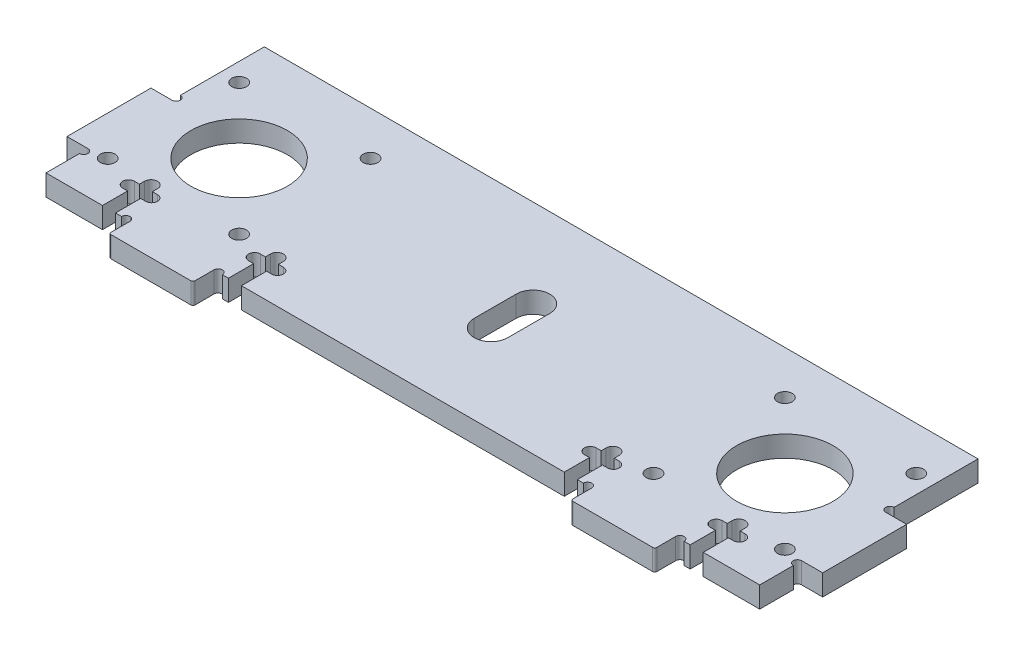
SolidWorks part; units mm, degrees
ref_plane "정면" through (0, 0, 0) normal (0, 0, 1) x (1, 0, 0)
ref_plane "윗면" through (0, 0, 0) normal (0, 1, 0) x (1, 0, 0)
ref_plane "우측면" through (0, 0, 0) normal (1, 0, 0) x (0, 0, -1)
sketch "스케치1" plane through (0, 0, 0) normal (0, 1, 0) x (1, 0, 0)
  line L1 (0, 0) -> (170, 0)
  line L2 (0, 0) -> (0, 52)
  line L3 (0, 52) -> (170, 52)
  line L4 (170, 0) -> (170, 52)
  dimension "D1" = 170
  dimension "D2" = 52
extrude "보스-돌출1" add sketch "스케치1" along normal blind 5
sketch "스케치2" plane through (0, 5, 0) normal (0, 1, 0) x (1, 0, 0)
  line L0 (85, 52) -> (85, 0) construction
  line L1 (170, 52) -> (0, 52) construction
  line L2 (0, 0) -> (170, 0) construction
  line L3 (150, 26) -> (20, 26) construction
  line L4 (134.35, 10.35) -> (165.65, 10.35) construction
  line L5 (134.35, 10.35) -> (134.35, 41.65) construction
  line L6 (134.35, 41.65) -> (165.65, 41.65) construction
  line L7 (165.65, 10.35) -> (165.65, 41.65) construction
  line L8 (134.35, 10.35) -> (165.65, 41.65) construction
  line L9 (134.35, 41.65) -> (165.65, 10.35) construction
  line L10 (170, 0) -> (170, 52) construction
  line L11 (35.65, 41.65) -> (4.35, 10.35) construction
  line L12 (35.65, 10.35) -> (4.35, 41.65) construction
  line L13 (4.35, 10.35) -> (4.35, 41.65) construction
  line L14 (35.65, 41.65) -> (4.35, 41.65) construction
  line L15 (35.65, 10.35) -> (35.65, 41.65) construction
  line L16 (35.65, 10.35) -> (4.35, 10.35) construction
  circle A0 centre (150, 26) radius 11.5
  circle A1 centre (165.65, 41.65) radius 1.75
  circle A2 centre (134.35, 41.65) radius 1.75
  circle A3 centre (165.65, 10.35) radius 1.75
  circle A4 centre (134.35, 10.35) radius 1.75
  circle A5 centre (35.65, 10.35) radius 1.75
  circle A6 centre (4.35, 10.35) radius 1.75
  circle A7 centre (35.65, 41.65) radius 1.75
  circle A8 centre (4.35, 41.65) radius 1.75
  circle A9 centre (20, 26) radius 11.5
  point P16 (170, 26)
  point P25 (85, 26)
  dimension "D1" = 23
  dimension "D3" = 3.5
  dimension "D2" = 31.3
  dimension "D4" = 20
extrude "컷-돌출1" cut sketch "스케치2" against normal blind 5
sketch "스케치3" plane through (0, 5, 0) normal (0, 1, 0) x (1, 0, 0)
  line L1 (0, 0) -> (170, 0) construction
  line L2 (130, 0) -> (150, 0)
  line L3 (130, 0) -> (130, -5)
  line L4 (130, -5) -> (150, -5)
  line L5 (150, 0) -> (150, -5)
  line L6 (130, -5) -> (40, -5) construction
  line L7 (20, 0) -> (40, 0)
  line L8 (20, 0) -> (20, -5)
  line L9 (20, -5) -> (40, -5)
  line L10 (40, 0) -> (40, -5)
  line L11 (150, -5) -> (170, -5) construction
  line L12 (170, -5) -> (170, 0) construction
  line L13 (0, 0) -> (0, -5) construction
  line L14 (0, -5) -> (20, -5) construction
  dimension "D1" = 20
  dimension "D2" = 20
  dimension "D3" = 5
extrude "보스-돌출2" add sketch "스케치3" against normal blind 5
sketch "스케치4" plane through (0, 5, 0) normal (0, 1, 0) x (1, 0, 0)
  line L0 (40, 0) -> (130, 0) construction
  line L1 (150, 0) -> (170, 0) construction
  line L2 (0, 0) -> (20, 0) construction
  circle A0 centre (129, 0) radius 1
  circle A1 centre (151, 0) radius 1
  circle A2 centre (19, 0) radius 1
  circle A3 centre (41, 0) radius 1
  dimension "D1" = 2
extrude "컷-돌출2" cut sketch "스케치4" against normal blind 5
sketch "스케치5" plane through (0, 5, 0) normal (0, 1, 0) x (1, 0, 0)
  line L0 (156.55, 0) -> (156.55, 6)
  line L1 (153.45, 10) -> (156.55, 10) construction
  line L2 (152.25, 6) -> (152.25, 8.8) construction
  line L3 (156.55, 6) -> (156.55, 8.8) construction
  line L4 (153.45, 0) -> (156.55, 0)
  line L5 (152.25, 8.8) -> (153.45, 8.8)
  line L6 (153.45, 0) -> (153.45, 6)
  line L7 (157.75, 8.8) -> (157.75, 6) construction
  line L8 (153.45, 6) -> (152.25, 6)
  line L9 (153.45, 8.8) -> (153.45, 6) construction
  line L10 (156.55, 8.8) -> (156.55, 10)
  line L11 (153.45, 6) -> (156.55, 6) construction
  line L12 (153.45, 8.8) -> (156.55, 8.8) construction
  line L13 (156.55, 8.8) -> (157.75, 8.8)
  line L14 (153.45, 8.8) -> (153.45, 10)
  line L15 (155, 10) -> (155, 12.1831) construction
  line L16 (157.75, 6) -> (156.55, 6)
  line L17 (126.55, 0) -> (126.55, 6)
  line L18 (123.45, 10) -> (126.55, 10) construction
  line L19 (122.25, 6) -> (122.25, 8.8) construction
  line L20 (126.55, 6) -> (126.55, 8.8) construction
  line L21 (123.45, 0) -> (126.55, 0)
  line L22 (122.25, 8.8) -> (123.45, 8.8)
  line L23 (123.45, 0) -> (123.45, 6)
  line L24 (127.75, 8.8) -> (127.75, 6) construction
  line L25 (123.45, 6) -> (122.25, 6)
  line L26 (123.45, 8.8) -> (123.45, 6) construction
  line L27 (126.55, 8.8) -> (126.55, 10)
  line L28 (123.45, 6) -> (126.55, 6) construction
  line L29 (123.45, 8.8) -> (126.55, 8.8) construction
  line L30 (126.55, 8.8) -> (127.75, 8.8)
  line L31 (123.45, 8.8) -> (123.45, 10)
  line L32 (125, 10) -> (125, 12.1831) construction
  line L33 (127.75, 6) -> (126.55, 6)
  line L34 (170, 0) -> (170, 52) construction
  line L35 (85, 52) -> (85, 0) construction
  line L36 (170, 52) -> (0, 52) construction
  line L37 (42, 0) -> (128, 0) construction
  line L38 (45, 10) -> (45, 12.1831) construction
  line L39 (46.55, 8.8) -> (43.45, 8.8) construction
  line L40 (46.55, 6) -> (43.45, 6) construction
  line L41 (46.55, 8.8) -> (46.55, 6) construction
  line L42 (42.25, 8.8) -> (42.25, 6) construction
  line L43 (43.45, 6) -> (43.45, 8.8) construction
  line L44 (47.75, 6) -> (47.75, 8.8) construction
  line L45 (46.55, 10) -> (43.45, 10) construction
  line L46 (15, 10) -> (15, 12.1831) construction
  line L47 (16.55, 8.8) -> (13.45, 8.8) construction
  line L48 (16.55, 6) -> (13.45, 6) construction
  line L49 (16.55, 8.8) -> (16.55, 6) construction
  line L50 (12.25, 8.8) -> (12.25, 6) construction
  line L51 (13.45, 6) -> (13.45, 8.8) construction
  line L52 (17.75, 6) -> (17.75, 8.8) construction
  line L53 (16.55, 10) -> (13.45, 10) construction
  line L54 (42.25, 6) -> (43.45, 6)
  line L55 (46.55, 8.8) -> (46.55, 10)
  line L56 (43.45, 8.8) -> (42.25, 8.8)
  line L57 (43.45, 8.8) -> (43.45, 10)
  line L58 (46.55, 6) -> (47.75, 6)
  line L59 (46.55, 0) -> (46.55, 6)
  line L60 (47.75, 8.8) -> (46.55, 8.8)
  line L61 (46.55, 0) -> (43.45, 0)
  line L62 (43.45, 0) -> (43.45, 6)
  line L63 (12.25, 6) -> (13.45, 6)
  line L64 (16.55, 8.8) -> (16.55, 10)
  line L65 (13.45, 8.8) -> (12.25, 8.8)
  line L66 (13.45, 8.8) -> (13.45, 10)
  line L67 (16.55, 6) -> (17.75, 6)
  line L68 (16.55, 0) -> (16.55, 6)
  line L69 (17.75, 8.8) -> (16.55, 8.8)
  line L70 (16.55, 0) -> (13.45, 0)
  line L71 (13.45, 0) -> (13.45, 6)
  arc A0 (156.55, 10) -> (153.45, 10) centre (155, 10) ccw
  arc A1 (152.25, 8.8) -> (152.25, 6) centre (152.25, 7.4) ccw
  arc A2 (157.75, 6) -> (157.75, 8.8) centre (157.75, 7.4) ccw
  arc A3 (126.55, 10) -> (123.45, 10) centre (125, 10) ccw
  arc A4 (122.25, 8.8) -> (122.25, 6) centre (122.25, 7.4) ccw
  arc A5 (127.75, 6) -> (127.75, 8.8) centre (127.75, 7.4) ccw
  arc A6 (42.25, 6) -> (42.25, 8.8) centre (42.25, 7.4) cw
  arc A7 (47.75, 8.8) -> (47.75, 6) centre (47.75, 7.4) cw
  arc A8 (43.45, 10) -> (46.55, 10) centre (45, 10) cw
  arc A9 (12.25, 6) -> (12.25, 8.8) centre (12.25, 7.4) cw
  arc A10 (17.75, 8.8) -> (17.75, 6) centre (17.75, 7.4) cw
  arc A11 (13.45, 10) -> (16.55, 10) centre (15, 10) cw
  dimension "D1" = 3.1
  dimension "D2" = 10
  dimension "D3" = 5.5
  dimension "D4" = 2.8
  dimension "D5" = 6
  dimension "D6" = 3.1
  dimension "D7" = 10
  dimension "D8" = 5.5
  dimension "D9" = 2.8
  dimension "D10" = 6
  dimension "D11" = 30
  dimension "D12" = 15
extrude "컷-돌출3" cut sketch "스케치5" against normal blind 10
fillet "필렛1" radius 0.5 4 edges at (20, 2.5, 5) (130, 2.5, 5) (150, 2.5, 5) (40, 2.5, 5)
sketch "스케치6" plane through (0, 5, 0) normal (0, 1, 0) x (1, 0, 0)
  line L0 (85, 52) -> (85, 0) construction
  line L1 (170, 52) -> (0, 52) construction
  line L2 (46.55, 0) -> (123.45, 0) construction
  line L3 (85, 21) -> (85, 31) construction
  line L4 (81, 21) -> (81, 31)
  line L5 (89, 21) -> (89, 31)
  arc A0 (81, 21) -> (89, 21) centre (85, 21) ccw
  arc A1 (89, 31) -> (81, 31) centre (85, 31) ccw
  point P8 (85, 26)
  dimension "D1" = 4
  dimension "D2" = 10
extrude "컷-돌출4" cut sketch "스케치6" against normal blind 10
sketch "스케치7" plane through (0, 5, 0) normal (0, 1, 0) x (1, 0, 0)
  line L0 (170, 0) -> (170, 52) construction
  line L1 (170, 30) -> (175, 30)
  line L2 (170, 30) -> (170, 10)
  line L3 (170, 10) -> (175, 10)
  line L4 (175, 30) -> (175, 10)
  line L5 (0, 52) -> (0, 0) construction
  line L6 (0, 30) -> (-5, 30)
  line L7 (0, 30) -> (0, 10)
  line L8 (0, 10) -> (-5, 10)
  line L9 (-5, 30) -> (-5, 10)
  line L10 (156.55, 0) -> (170, 0) construction
  dimension "D1" = 5
  dimension "D2" = 10
  dimension "D3" = 20
extrude "보스-돌출3" add sketch "스케치7" against normal blind 5
sketch "스케치8" plane through (0, 5, 0) normal (0, 1, 0) x (1, 0, 0)
  line L0 (170, 0) -> (170, 10) construction
  line L1 (170, 30) -> (170, 52) construction
  line L2 (0, 10) -> (0, 0) construction
  line L3 (0, 52) -> (0, 30) construction
  circle A0 centre (170, 9) radius 1
  circle A1 centre (170, 31) radius 1
  circle A2 centre (0, 9) radius 1
  circle A3 centre (0, 31) radius 1
  dimension "D1" = 2
extrude "컷-돌출5" cut sketch "스케치8" against normal blind 5
